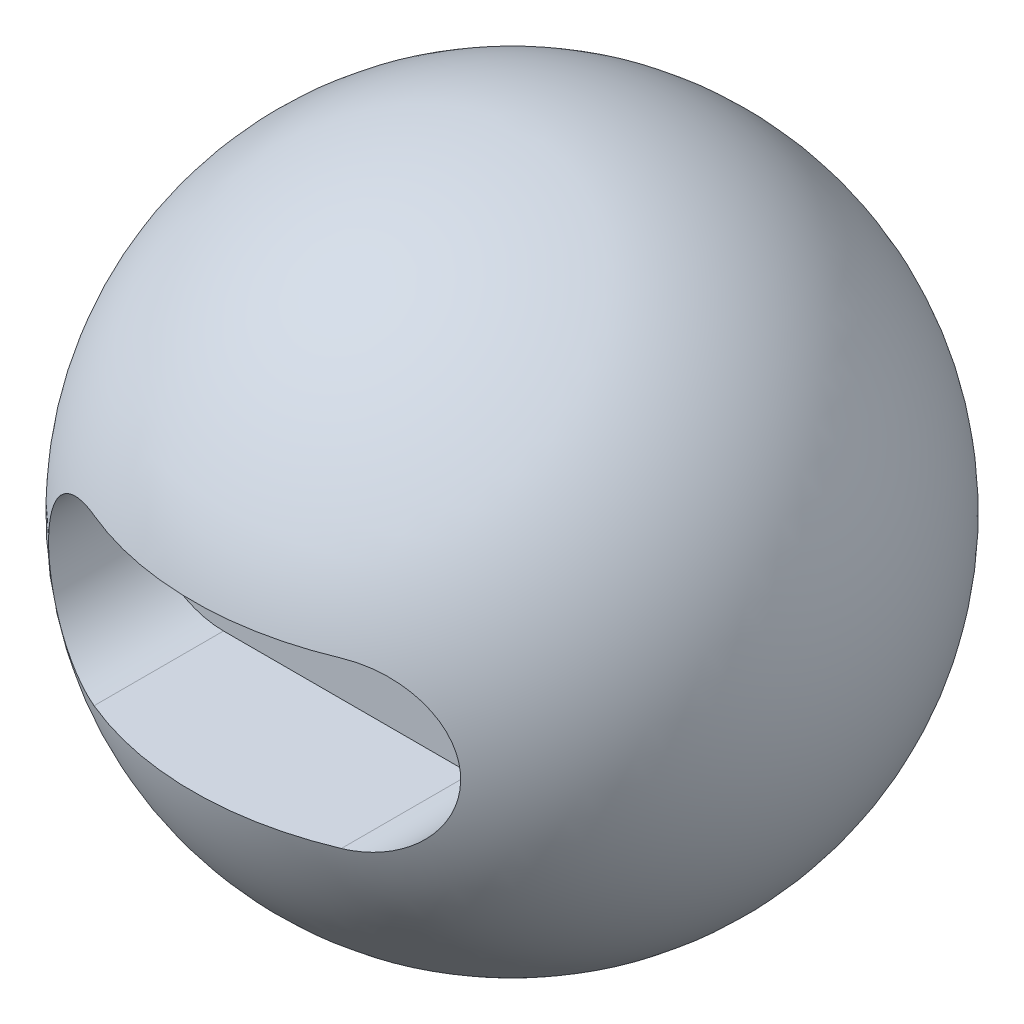
SolidWorks part; units mm, degrees
ref_plane "Front Plane" through (0, 0, 0) normal (0, 0, 1) x (1, 0, 0)
ref_plane "Top Plane" through (0, 0, 0) normal (0, 1, 0) x (1, 0, 0)
ref_plane "Right Plane" through (0, 0, 0) normal (1, 0, 0) x (0, 0, -1)
sketch "Sketch1" plane through (0, 0, 0) normal (0, 0, 1) x (1, 0, 0)
  line L0 (0, -1000) -> (0, 1000)
  arc A0 (0, 1000) -> (0, -1000) centre (0, 0) ccw
  point P6 (0, 0)
  dimension "D1" = 2000
revolve "Revolve1" add sketch "Sketch1" angle 360 about L0
ref_plane "Plane2" through (0, 0, 1000) normal (0, 0, 1) x (1, 0, 0)
sketch "Sketch7" plane through (0, 0, 1000) normal (0, 0, 1) x (1, 0, 0)
  line L0 (-375, 0) -> (375, 0) construction
  line L1 (-375, 250) -> (375, 250)
  line L2 (-375, -250) -> (375, -250)
  arc A0 (-375, 250) -> (-375, -250) centre (-375, 0) ccw
  arc A1 (375, -250) -> (375, 250) centre (375, 0) ccw
  point P3 (0, 0)
  point P8 (0, 0)
  dimension "D2" = 250
  dimension "D1" = 750
extrude "Cut-Extrude2" cut sketch "Sketch7" against normal blind 500
